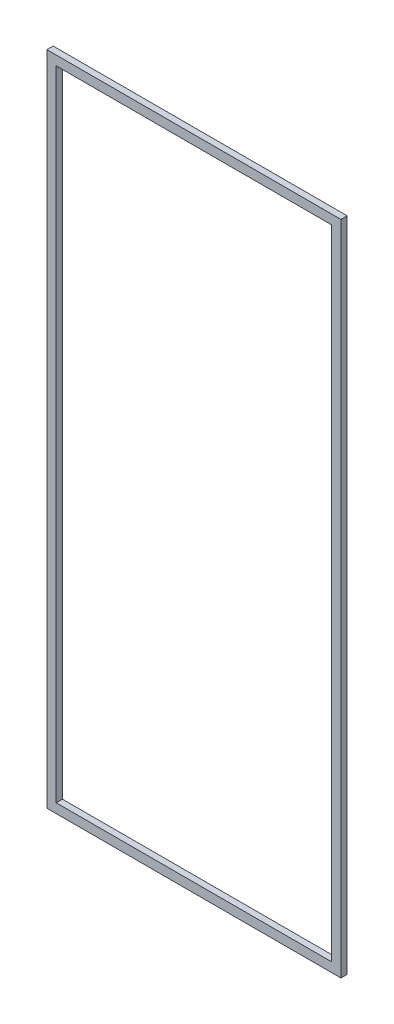
SolidWorks part; units mm, degrees
ref_plane "Спереди" through (0, 0, 0) normal (0, 0, 1) x (1, 0, 0)
ref_plane "Сверху" through (0, 0, 0) normal (0, 1, 0) x (1, 0, 0)
ref_plane "Справа" through (0, 0, 0) normal (1, 0, 0) x (0, 0, -1)
sketch "Эскиз1" plane through (0, 0, 0) normal (0, 0, 1) x (1, 0, 0)
  line L1 (-235, 525) -> (235, 525)
  line L2 (-235, 525) -> (-235, -525)
  line L3 (-235, -525) -> (235, -525)
  line L4 (235, 525) -> (235, -525)
  line L5 (-235, 525) -> (235, -525) construction
  line L6 (-235, -525) -> (235, 525) construction
  point P0 (0, 0)
extrude "Вытянуть-Тонкостенный1" add sketch "Эскиз1" along normal blind 10 thin thin type one direction reverse wall 15
